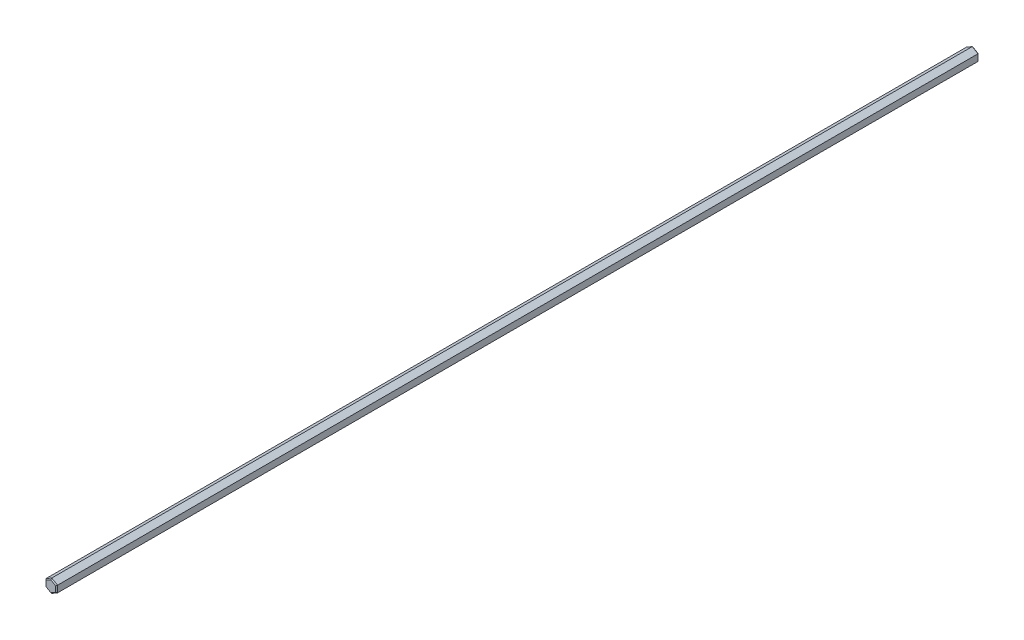
SolidWorks part; units mm, degrees
ref_plane "Front Plane" through (0, 0, 0) normal (0, 0, 1) x (1, 0, 0)
ref_plane "Top Plane" through (0, 0, 0) normal (0, 1, 0) x (1, 0, 0)
ref_plane "Right Plane" through (0, 0, 0) normal (1, 0, 0) x (0, 0, -1)
ref_plane "Plane1" through (0, 0, 75) normal (0, 0, 1) x (1, 0, 0)
sketch "Sketch1" plane through (0, 0, 75) normal (0, 0, 1) x (1, 0, 0)
  line L0 (0, -2.8868) -> (2.5, -1.4434)
  line L1 (2.5, -1.4434) -> (2.5, 1.4434)
  line L2 (2.5, 1.4434) -> (0, 2.8868)
  line L3 (0, 2.8868) -> (-2.5, 1.4434)
  line L4 (-2.5, 1.4434) -> (-2.5, -1.4434)
  line L5 (-2.5, -1.4434) -> (0, -2.8868)
extrude "Boss-Extrude1" add sketch "Sketch1" against normal blind 400
chamfer "Chamfer1" distance 0.4 angle 45 12 edges at (-2.5, 0, -325) (-1.25, -2.1651, -325) (-1.25, 2.1651, -325) (1.25, -2.1651, -325) (1.25, 2.1651, -325) (2.5, 0, -325) (-1.25, 2.1651, 75) (-2.5, 0, 75) (1.25, 2.1651, 75) (-1.25, -2.1651, 75) (2.5, 0, 75) (1.25, -2.1651, 75)
